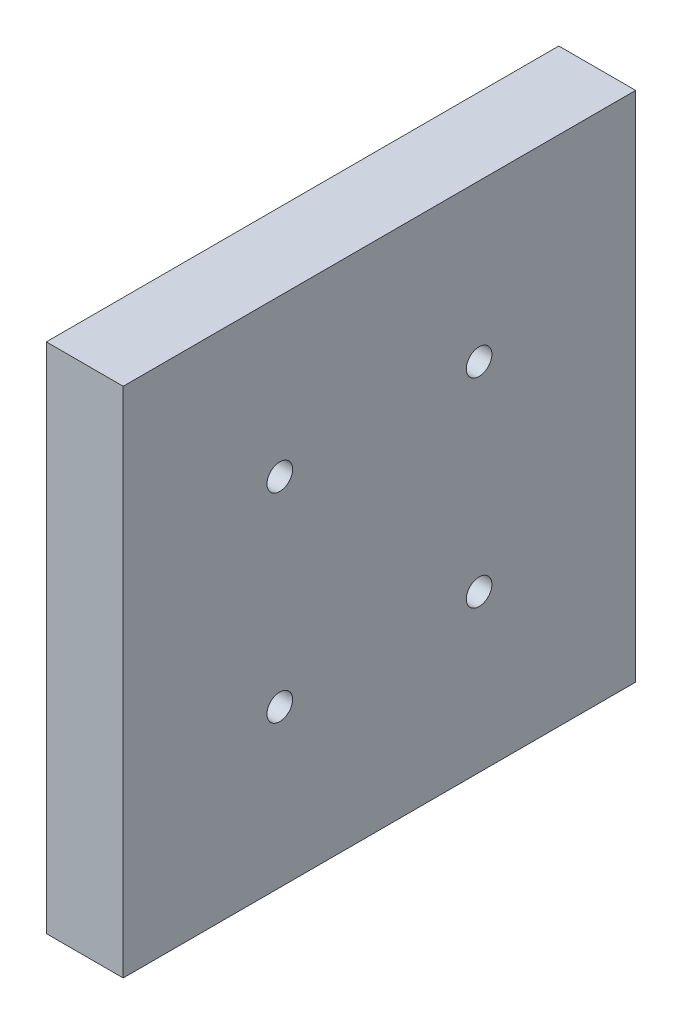
SolidWorks part; units mm, degrees
ref_plane "Ebene vorne" through (0, 0, 0) normal (0, 0, 1) x (1, 0, 0)
ref_plane "Ebene oben" through (0, 0, 0) normal (0, 1, 0) x (1, 0, 0)
ref_plane "Ebene rechts" through (0, 0, 0) normal (1, 0, 0) x (0, 0, -1)
sketch "Sketch2" plane through (0, 0, 0) normal (1, 0, 0) x (0, 0, -1)
  line L0 (-81.0651, 0) -> (92.8994, 0) construction
  line L1 (-50, 50) -> (50, 50)
  line L2 (-50, 50) -> (-50, -50)
  line L3 (-50, -50) -> (50, -50)
  line L4 (50, 50) -> (50, -50)
  line L5 (0, 88.4615) -> (0, -84.3195) construction
  dimension "D1" = 100
  dimension "D2" = 100
extrude "Boss-Extrude1" add sketch "Sketch2" along normal blind 15
sketch "Sketch3" plane through (15, 0, 0) normal (1, 0, 0) x (0, 0, -1)
  line L2 (-76.29, 0) -> (76.29, 0) construction
  line L4 (-50, 50) -> (50, -50) construction
  line L5 (0, 50) -> (0, -50) construction
  line L6 (50, 50) -> (-50, 50) construction
  line L7 (-50, -50) -> (50, -50) construction
  circle A0 centre (0, 0) radius 76.29 construction
  circle A1 centre (-19.4454, 19.4454) radius 2.5
  circle A2 centre (19.4454, 19.4454) radius 2.5
  circle A3 centre (19.4454, -19.4454) radius 2.5
  circle A4 centre (-19.4454, -19.4454) radius 2.5
  point P3 (0, 0)
  point P14 (0, 0)
  point P15 (0, 0)
  point P17 (0, 0)
  point P27 (0, 0)
  dimension "D1" = 152.58
  dimension "D2" = 5
  dimension "D3" = 55
  dimension "D4" = 4
extrude "Cut-Extrude1" cut sketch "Sketch3" against normal blind 15
